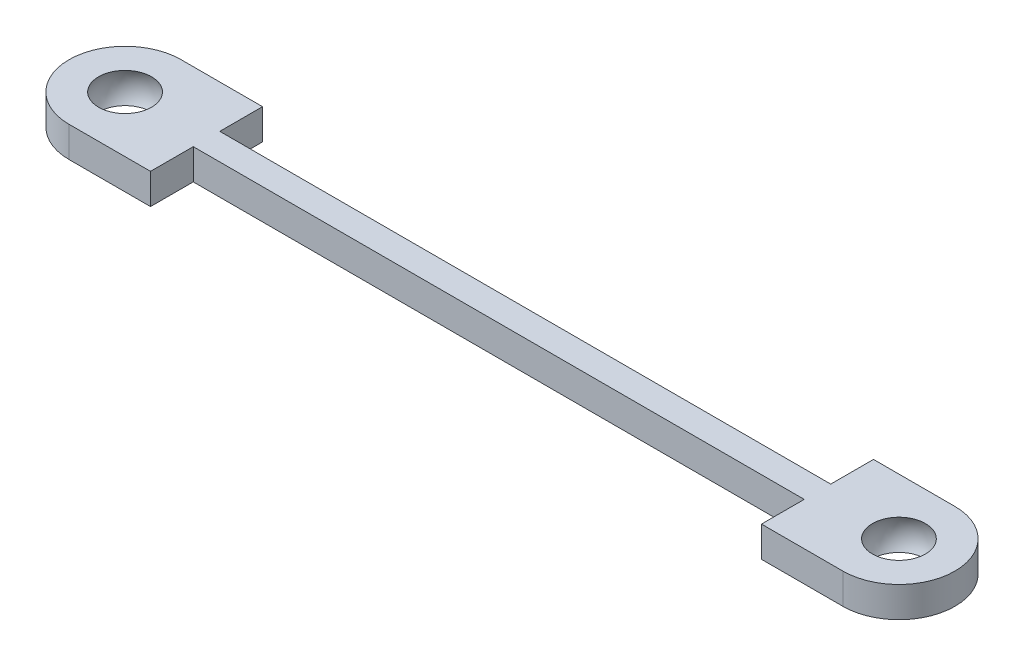
SolidWorks part; units mm, degrees
ref_plane "Front Plane" through (0, 0, 0) normal (0, 0, 1) x (1, 0, 0)
ref_plane "Top Plane" through (0, 0, 0) normal (0, 1, 0) x (1, 0, 0)
ref_plane "Right Plane" through (0, 0, 0) normal (1, 0, 0) x (0, 0, -1)
sketch "Sketch1" plane through (0, 0, 0) normal (0, 1, 0) x (1, 0, 0)
  line L0 (-19, 0) -> (19, 0) construction
  line L1 (-19, 0) -> (19, 0) construction
  line L2 (-19, 2.75) -> (19, 2.75)
  line L3 (-19, -2.75) -> (19, -2.75)
  line L4 (15, -2.75) -> (15, 2.75)
  line L5 (-15, -0.6507) -> (15, -0.6507)
  line L6 (-15, -0.6507) -> (-15, 0.6507)
  line L7 (-15, 0.6507) -> (15, 0.6507)
  line L8 (15, -0.6507) -> (15, 0.6507)
  line L9 (-15, -0.6507) -> (15, 0.6507) construction
  line L10 (-15, 0.6507) -> (15, -0.6507) construction
  line L11 (-15, -2.75) -> (-15, 2.75)
  line L12 (-20.5, 0) -> (-17.5, 0)
  line L13 (17.5, 0) -> (20.5, 0)
  circle A0 centre (-19, 0) radius 1.5
  circle A1 centre (19, 0) radius 1.5
  arc A2 (-19, 2.75) -> (-19, -2.75) centre (-19, 0) ccw
  arc A3 (19, -2.75) -> (19, 2.75) centre (19, 0) ccw
  point P4 (0, 0)
  point P10 (0, 0)
  dimension "D1" = 3
  dimension "D4" = 2.75
  dimension "D2" = 4
  dimension "D3" = 30
extrude "Boss-Extrude1" add sketch "Sketch1" along normal blind 0.75 and the other way blind 0.75 contours L2 A2 L3 L11 L6 A0 | L3 A3 L2 L4 A1 | A0 | A1 | L7 L6 L5 L4 | L12 A0 | L13 A1 region at (-17, 0, -2.6629) region at (17, 0, -2.6629) region at (0, 0, 0) region at (-19, 0, -0.6366) region at (-19, 0, 0.6366) region at (19, 0, -0.6366) region at (19, 0, 0.6366)
revolve "Cut-Revolve1" cut sketch "Sketch1<3>" angle 360 about L0 region at (-19, 0, 0.6366) region at (19, 0, 0.6366)
sketch "Sketch1<3>" plane through (0, 0, 0) normal (0, 1, 0) x (1, 0, 0) same geometry as "Sketch1"
